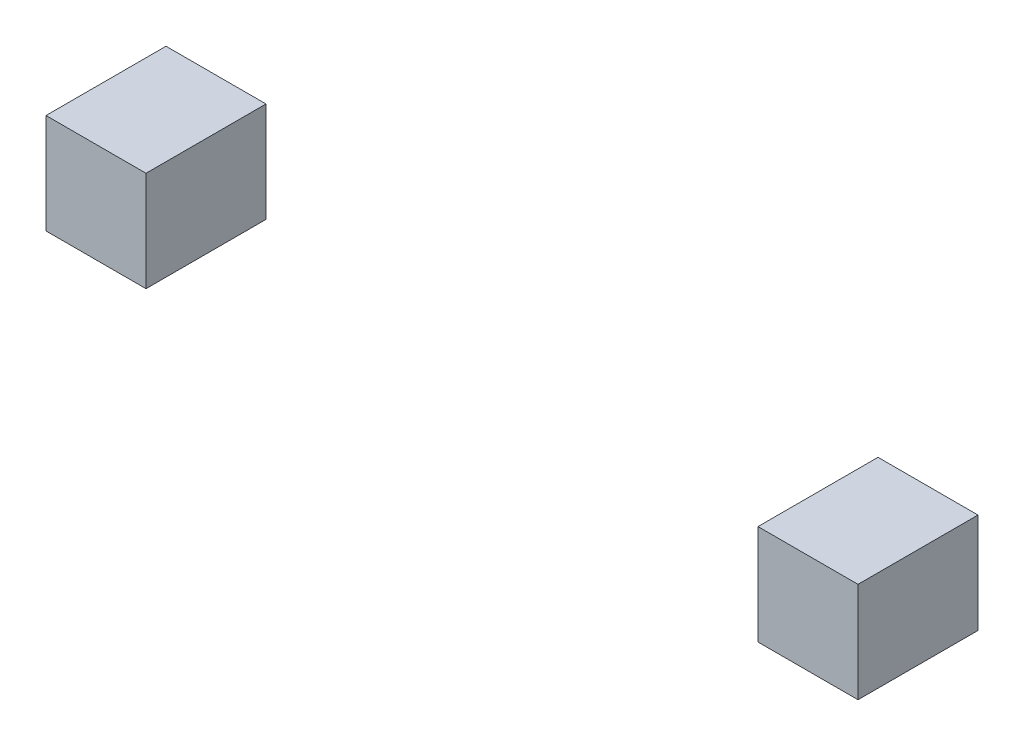
SolidWorks part; units mm, degrees
ref_plane "Front Plane" through (0, 0, 0) normal (0, 0, 1) x (1, 0, 0)
ref_plane "Top Plane" through (0, 0, 0) normal (0, 1, 0) x (1, 0, 0)
ref_plane "Right Plane" through (0, 0, 0) normal (1, 0, 0) x (0, 0, -1)
sketch "Sketch1" plane through (0, 0, 0) normal (0, 0, 1) x (1, 0, 0)
  line L1 (305, 710.27) -> (230, 710.27)
  line L2 (305, 710.27) -> (305, 635.27)
  line L3 (305, 635.27) -> (230, 635.27)
  line L4 (230, 710.27) -> (230, 635.27)
  line L5 (-304, 710.27) -> (-229, 710.27)
  line L6 (-304, 710.27) -> (-304, 635.27)
  line L7 (-304, 635.27) -> (-229, 635.27)
  line L8 (-229, 710.27) -> (-229, 635.27)
  dimension "D1" = 75
  dimension "D2" = 75
  dimension "D3" = 75
  dimension "D4" = 75
extrude "Boss-Extrude1" add sketch "Sketch1" along normal blind 90
